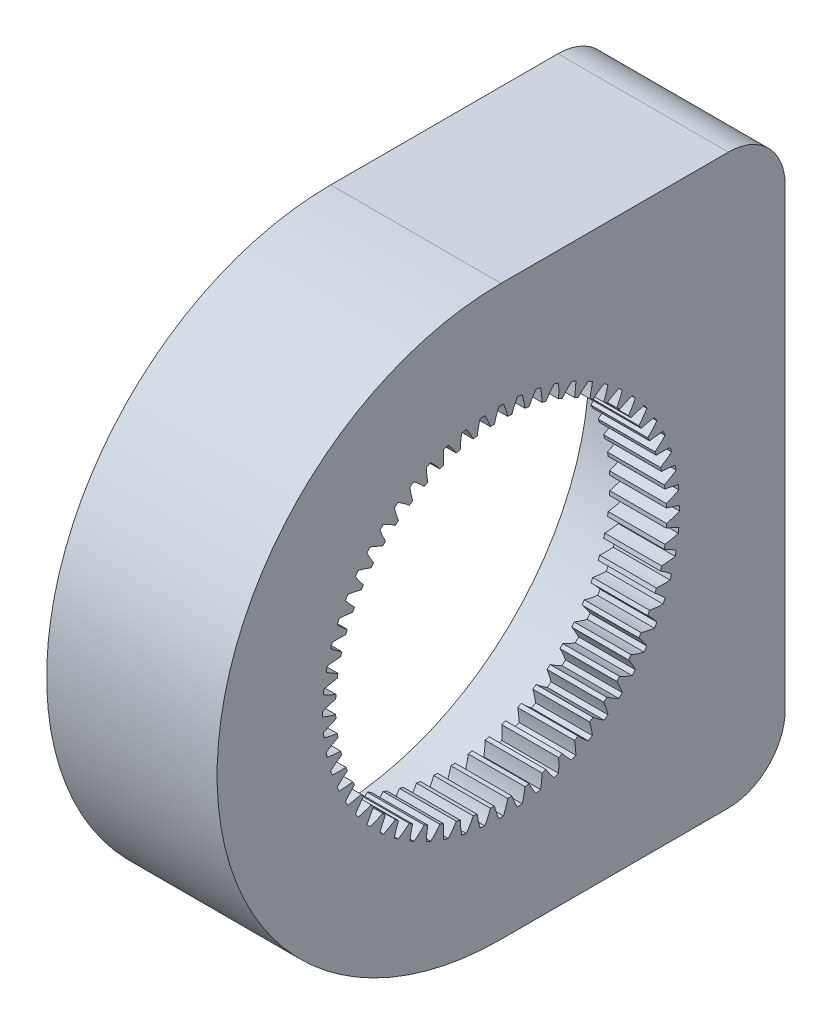
SolidWorks part; units mm, degrees
ref_plane "Plane1" through (0, 0, 0) normal (0, 0, 1) x (1, 0, 0)
ref_plane "Plane2" through (0, 0, 0) normal (0, 1, 0) x (1, 0, 0)
ref_plane "Plane3" through (0, 0, 0) normal (1, 0, 0) x (0, 0, -1)
other "Configuration Table"
sketch "HoldingSke" plane through (0, 0, 0) normal (0, 1, 0) x (1, 0, 0)
  line L0 (0, 0) -> (0.4975, -0.8617)
  line L1 (-15, 0) -> (100, 0) construction
  line L2 (0, 0) -> (-2.1039, 2.3779)
  line L3 (0, 0) -> (-11.863, 4.5341)
  line L4 (0, 0) -> (4.318, 7.479)
  line L5 (0, 0) -> (-23.7986, -8.8762)
  line L6 (0, 0) -> (-10.5278, -7.1032)
  line L7 (-2.1039, 2.3779) -> (3.3635, 27.1825)
  line L8 (-76.2, 3.3829) -> (-54.61, 3.3829)
  line L9 (-67.7845, 28.3722) -> (-49.3413, 33.142)
  line L10 (-76.2, 71.12) -> (104.1128, 71.12)
  line L11 (0, 0) -> (-10, 0)
  line L12 (-76.2, 101.6) -> (-76.162, 101.6)
  line L13 (24.9733, 27.94) -> (52.9518, 28.4284)
  line L14 (24.9733, 27.94) -> (24.9743, 27.94)
  line L15 (24.9733, 27.94) -> (100.4006, 29.5858)
  circle A0 centre (0, 0) radius 50
  circle A1 centre (0, 0) radius 12.7
  circle A2 centre (0, 0) radius 12.7
  dimension "Num_teeth" = 60
  dimension "Pitch_radius" = 180.3128
  dimension "Width" = 10
  dimension "Diameter" = 100
sketch "BasProSke" plane through (0, 0, 0) normal (0, 1, 0) x (1, 0, 0)
  line L0 (-10, 0) -> (60, 0) construction
  line L1 (0, 29.145) -> (0, 50)
  line L2 (0, 29.145) -> (10, 29.145)
  line L3 (10, 29.145) -> (10, 50)
  line L4 (10, 50) -> (0, 50)
  dimension "Thickness" = 10
  dimension "Diameter" = 100
revolve "Base-Revolve" add sketch "BasProSke" angle 360 about L0
sketch "TooCutSke" plane through (0, 0, 0) normal (1, 0, 0) x (0, 0, -1)
  line L3 (0.8842, 30.137) -> (0.8842, 53.6633) construction
  line L4 (0, 0) -> (0, 59.563) construction
  line L5 (0, 0) -> (-3.576, 68.2339) construction
  line L6 (-13.4917, 25.5997) -> (36.416, 28.2152) construction
  circle A0 centre (0, 0) radius 30.15 construction
  circle A1 centre (0, 0) radius 31.4072 construction
  circle A2 centre (0, 0) radius 26.2707 construction
  circle A3 centre (0, 0) radius 29.1196 construction
  arc A4 (1.1722, 29.096) -> (0.4209, 31.4044) centre (-13.4917, 25.5997) ccw
  arc A5 (1.1722, 29.096) -> (-1.1722, 29.096) centre (0, 0) ccw
  arc A6 (0.4209, 31.4044) -> (-0.4209, 31.4044) centre (0, 0) ccw
  arc A7 (-0.4209, 31.4044) -> (-1.1722, 29.096) centre (13.4917, 25.5997) ccw
extrude "ToothCut" cut sketch "TooCutSke" along normal through all
fillet "Breaks" [suppressed] radius 0.1005
fillet "RootFillets" [suppressed] radius 0.2522
pattern_circular "TeethCuts" count 60 every 6 about axis through (-10, 0, 0) along (1, 0, 0) of "RootFillets", "Breaks", "ToothCut"
sketch "Sketch4" plane through (0, 0, 0) normal (-1, 0, 0) x (0, 0, 1)
  circle A0 centre (0, 0) radius 50
  circle A1 centre (0, 0) radius 45.5
  circle A2 centre (0, 0) radius 50 construction
  dimension "D1" = 91
extrude "Boss-Extrude3" add sketch "Sketch4" along normal blind 20
sketch "Sketch7" plane through (10, 0, 0) normal (1, 0, 0) x (0, 0, -1)
  line L0 (0, 50) -> (50, 50)
  line L1 (50, 50) -> (50, 0)
  circle A0 centre (0, 0) radius 50 construction
  arc A1 (50, 0) -> (0, 50) centre (0, 0) ccw
extrude "Boss-Extrude5" add sketch "Sketch7" against normal up to surface (30 mm away) up to face at (-20, 0, 50)
sketch "Sketch10" plane through (10, 0, 0) normal (1, 0, 0) x (0, 0, -1)
  line L0 (0, -50) -> (50, -50)
  line L1 (50, -50) -> (50, 0)
  line L2 (50, 0) -> (50, 50) construction
  arc A0 (0, 50) -> (50, 0) centre (0, 0) ccw construction
  arc A1 (0, -50) -> (50, 0) centre (0, 0) ccw
  dimension "D1" = 180
extrude "Boss-Extrude6" add sketch "Sketch10" against normal up to surface (30 mm away) up to face at (-20, 13.2149, -13.2149)
fillet "Fillet1" radius 10 2 edges at (-5, 50, -50) (-5, -50, -50)
sketch "Sketch14" plane through (0, 0, 0) normal (-1, 0, 0) x (0, 0, 1)
  circle A0 centre (0, 0) radius 43.5
  circle A1 centre (0, 0) radius 45.5 construction
  circle A2 centre (0, 0) radius 45.5
  dimension "D1" = 2
extrude "Boss-Extrude7" add sketch "Sketch14" along normal blind 6
equation "' \"Module@HoldingSke\" = 6.35"
equation "' \"Num_teeth@HoldingSke\" = 24"
equation "' \"Ap@HoldingSke\" =  14.5"
equation "' \"Ap@HoldingSke\" = 14.5"
equation "' \"Width@HoldingSke\" = 12"
equation "' \"Diameter@HoldingSke\" = 8 * 25.4"
equation "' \"Show_teeth@HoldingSke\" = 100"
equation "' \"Backlash@HoldingSke\" = 0.009 * 25.4"
equation "' \"Addendum_fac@HoldingSke\" = 1.0"
equation "' \"Dedendum_fac@HoldingSke\" = 1.25"
equation "' \"Dedendum_add@HoldingSke\" = 0.00005 * 25.4"
equation "' \"Clearance_fac@HoldingSke\" = 0.25"
equation "\"Pitch@HoldingSke\" = 1 / \"Module@HoldingSke\" "
equation "\"Overcut_dia@TooCutSke\" = (\"Num_teeth@HoldingSke\" - 2 * \"Addendum_fac@HoldingSke\") / \"Pitch@HoldingSke\" - 0.002 * 25.4"
equation "\"Pitch_dia@TooCutSke\" = \"Num_teeth@HoldingSke\" / \"Pitch@HoldingSke\""
equation "\"Base_dia@TooCutSke\" = \"Num_teeth@HoldingSke\" / \"Pitch@HoldingSke\" * cos((\"Ap@HoldingSke\"  * 3.14159265 / 180)) * 0.90"
equation "\"Root_dia@TooCutSke\" = \"Num_teeth@HoldingSke\"  / \"Pitch@HoldingSke\" + 2 *  \"Dedendum_fac@HoldingSke\"/ \"Pitch@HoldingSke\" + \"Dedendum_add@HoldingSke\" * 2"
equation "\"Half_ang@TooCutSke\" = 180 / \"Num_teeth@HoldingSke\""
equation "\"Half_CT@TooCutSke\" = \"Num_teeth@HoldingSke\" / \"Pitch@HoldingSke\" * sin((3.14159265 / 2 / \"Num_teeth@HoldingSke\")) / 2 + 10 * \"Backlash@HoldingSke\" / 4"
equation "\"Flank_rad@TooCutSke\" = \"Num_teeth@HoldingSke\" / \"Pitch@HoldingSke\" / 4"
equation "\"Radius@RootFillets\"= \"Clearance_fac@HoldingSke\" / \"Pitch@HoldingSke\" + \"Dedendum_add@HoldingSke\""
equation "\"Break_rad@Breaks\" = 0.02 / \"Pitch@HoldingSke\" * 5"
equation "\"Num_teeth@TeethCuts\" = int( \"Show_teeth@HoldingSke\" ) + 1"
equation "\"Num_teeth@TeethCuts\" = ((sgn( \"Num_teeth@TeethCuts\" - \"Num_teeth@HoldingSke\" )-1)*( \"Num_teeth@TeethCuts\" - \"Num_teeth@HoldingSke\" ))/-2+ \"Num_teeth@HoldingSke\""
equation "\"Num_teeth@TeethCuts\" = ((sgn( \"Num_teeth@TeethCuts\" - 2.0)+1)*( \"Num_teeth@TeethCuts\" - 2.0))/2 +2.0"
equation "\"Angle@TeethCuts\" = 360.0 / \"Num_teeth@HoldingSke\""
equation "\"Diameter@BasProSke\" = \"Num_teeth@HoldingSke\"  / \"Pitch@HoldingSke\" + 2 *  \"Dedendum_fac@HoldingSke\"/ \"Pitch@HoldingSke\" + \"Dedendum_add@HoldingSke\" * 2 + 0.002 * 25.4"
equation "\"Diameter@BasProSke\" = ((sgn( \"Diameter@BasProSke\"  - \"Diameter@HoldingSke\" )+1)*( \"Diameter@BasProSke\"  - \"Diameter@HoldingSke\" ))/2 + \"Diameter@HoldingSke\""
equation "\"Inside_diameter@BasProSke\" =  (\"Num_teeth@HoldingSke\" - 2 * \"Addendum_fac@HoldingSke\") / \"Pitch@HoldingSke\" "
equation "\"Thickness@BasProSke\"  = \"Width@HoldingSke\""
